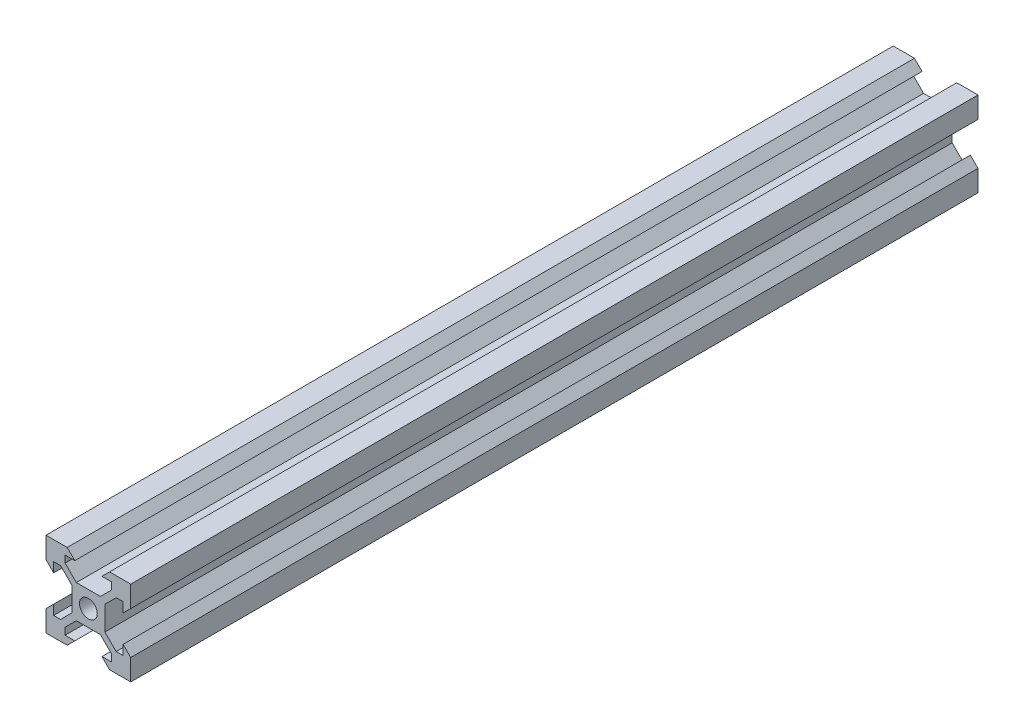
SolidWorks part; units mm, degrees
material "6063-T5"
ref_plane "Front Plane" through (0, 0, 0) normal (0, 0, 1) x (1, 0, 0)
ref_plane "Top Plane" through (0, 0, 0) normal (0, 1, 0) x (1, 0, 0)
ref_plane "Right Plane" through (0, 0, 0) normal (1, 0, 0) x (0, 0, -1)
sketch "Sketch1" plane through (0, 0, 0) normal (0, 0, 1) x (1, 0, 0)
  line L0 (-10, 10) -> (-5, 10)
  line L1 (10, -10) -> (-10, -10) construction
  line L2 (10, -10) -> (10, 10) construction
  line L3 (10, 10) -> (-10, 10) construction
  line L4 (-10, -10) -> (-10, 10) construction
  line L5 (10, -10) -> (-10, 10) construction
  line L6 (10, 10) -> (-10, -10) construction
  line L7 (-5, 10) -> (-3.2, 8.2)
  line L8 (-3.2, 8.2) -> (-5.4993, 8.2)
  line L9 (-5.4993, 8.2) -> (-5.4993, 6.56)
  line L10 (-2.84, 3.9007) -> (2.84, 3.9007)
  line L11 (0, 3.9007) -> (0, 2.1) construction
  line L12 (-5.4993, 6.56) -> (-2.84, 3.9007)
  line L13 (0, 0) -> (0, -13.2939) construction
  line L14 (0, 0) -> (-17.0802, 0) construction
  line L15 (-10, 10) -> (-10, 5)
  line L16 (-10, 5) -> (-8.2, 3.2)
  line L17 (-8.2, 3.2) -> (-8.2, 5.4993)
  line L18 (-8.2, 5.4993) -> (-6.56, 5.4993)
  line L19 (-6.56, 5.4993) -> (-3.9007, 2.84)
  line L20 (-3.9007, 2.84) -> (-3.9007, -2.84)
  line L21 (-3.2, -8.2) -> (-5.4993, -8.2)
  line L22 (-5.4993, -8.2) -> (-5.4993, -6.56)
  line L23 (-5, -10) -> (-3.2, -8.2)
  line L24 (-10, -10) -> (-5, -10)
  line L25 (-10, -10) -> (-10, -5)
  line L26 (-10, -5) -> (-8.2, -3.2)
  line L27 (-8.2, -3.2) -> (-8.2, -5.4993)
  line L28 (-8.2, -5.4993) -> (-6.56, -5.4993)
  line L29 (-6.56, -5.4993) -> (-3.9007, -2.84)
  line L30 (-5.4993, -6.56) -> (-2.84, -3.9007)
  line L31 (-2.84, -3.9007) -> (2.84, -3.9007)
  line L32 (5.4993, 6.56) -> (2.84, 3.9007)
  line L33 (3.2, 8.2) -> (5.4993, 8.2)
  line L34 (5.4993, 8.2) -> (5.4993, 6.56)
  line L35 (5, 10) -> (3.2, 8.2)
  line L36 (10, 10) -> (5, 10)
  line L37 (10, 10) -> (10, 5)
  line L38 (10, 5) -> (8.2, 3.2)
  line L39 (8.2, 3.2) -> (8.2, 5.4993)
  line L40 (8.2, 5.4993) -> (6.56, 5.4993)
  line L41 (6.56, 5.4993) -> (3.9007, 2.84)
  line L42 (3.9007, 2.84) -> (3.9007, -2.84)
  line L43 (6.56, -5.4993) -> (3.9007, -2.84)
  line L44 (8.2, -5.4993) -> (6.56, -5.4993)
  line L45 (8.2, -3.2) -> (8.2, -5.4993)
  line L46 (10, -5) -> (8.2, -3.2)
  line L47 (10, -10) -> (10, -5)
  line L48 (10, -10) -> (5, -10)
  line L49 (5, -10) -> (3.2, -8.2)
  line L50 (3.2, -8.2) -> (5.4993, -8.2)
  line L51 (5.4993, -8.2) -> (5.4993, -6.56)
  line L52 (5.4993, -6.56) -> (2.84, -3.9007)
  circle A0 centre (0, 0) radius 2.1
  arc A1 (0, -2.1) -> (0, 2.1) centre (0, 0) cw construction
  point P0 (0, 0)
  point P25 (-3.9007, 0)
  point P35 (0, 0)
  point P56 (0, -3.9007)
  dimension "D2" = 4.2
  dimension "D1" = 20
  dimension "D3" = 1.64
  dimension "D4" = 1.8
  dimension "D5" = 45
  dimension "D6" = 1.5
  dimension "D7" = 5.68
  dimension "D8" = 5
extrude "Boss-Extrude1" add sketch "Sketch1" along normal mid plane 200
